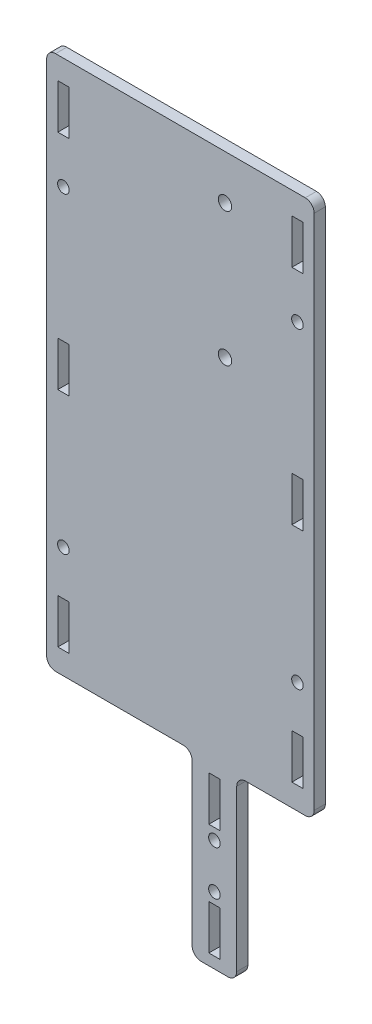
SolidWorks part; units mm, degrees
ref_plane "Front Plane" through (0, 0, 0) normal (0, 0, 1) x (1, 0, 0)
ref_plane "Top Plane" through (0, 0, 0) normal (0, 1, 0) x (1, 0, 0)
ref_plane "Right Plane" through (0, 0, 0) normal (1, 0, 0) x (0, 0, -1)
sketch "Sketch1" plane through (0, 0, 0) normal (0, 0, 1) x (1, 0, 0)
  line L0 (47.7875, -50.8) -> (47.7875, 0) construction
  line L1 (0, 0) -> (76.2, 0)
  line L2 (0, 0) -> (0, 152.4)
  line L3 (0, 152.4) -> (76.2, 152.4)
  line L4 (76.2, 0) -> (76.2, 152.4)
  line L5 (41.4375, 0) -> (54.1375, 0)
  line L6 (41.4375, 0) -> (41.4375, -50.8)
  line L7 (41.4375, -50.8) -> (54.1375, -50.8)
  line L8 (54.1375, 0) -> (54.1375, -50.8)
  line L9 (41.4375, -25.4) -> (54.1375, -25.4) construction
  line L10 (46.2, -34.925) -> (49.375, -34.925)
  line L11 (46.2, -34.925) -> (46.2, -47.625)
  line L12 (46.2, -47.625) -> (49.375, -47.625)
  line L13 (49.375, -34.925) -> (49.375, -47.625)
  line L14 (46.2, -34.925) -> (49.375, -47.625) construction
  line L15 (46.2, -47.625) -> (49.375, -34.925) construction
  line L16 (46.2, -3.175) -> (49.375, -15.875) construction
  line L17 (46.2, -15.875) -> (49.375, -3.175) construction
  line L18 (49.375, -15.875) -> (49.375, -3.175)
  line L19 (46.2, -3.175) -> (49.375, -3.175)
  line L20 (46.2, -15.875) -> (46.2, -3.175)
  line L21 (46.2, -15.875) -> (49.375, -15.875)
  point P11 (47.7875, -41.275)
  point P22 (47.7875, -9.525)
  dimension "D1" = 76.2
  dimension "D2" = 152.4
  dimension "D3" = 50.8
  dimension "D4" = 12.7
  dimension "D5" = 3.175
  dimension "D6" = 19.05
  dimension "D7" = 12.7
  dimension "D8" = 30
extrude "Boss-Extrude1" add sketch "Sketch1" along normal blind 3.175 contours L1 L4 L3 L2 | L8 L1 L6 L7 L21 L20 L19 L18 L10 L13 L12 L11 region at (38.1, 76.2, 0) region at (47.7875, -25.4, 0)
sketch "Sketch3" plane through (0, 0, 3.175) normal (0, 0, 1) x (1, 0, 0)
  line L0 (38.1, 152.4) -> (38.1, 0) construction
  line L1 (0, 76.2) -> (76.2, 76.2) construction
  line L2 (4.7625, 19.05) -> (4.7625, 133.35) construction
  line L3 (3.175, 146.05) -> (6.35, 146.05)
  line L4 (3.175, 146.05) -> (3.175, 133.35)
  line L5 (3.175, 133.35) -> (6.35, 133.35)
  line L6 (6.35, 146.05) -> (6.35, 133.35)
  line L7 (3.175, 19.05) -> (6.35, 19.05)
  line L8 (0, 0) -> (41.4375, 0)
  line L9 (41.4375, 0) -> (41.4375, -50.8)
  line L10 (41.4375, -50.8) -> (54.1375, -50.8)
  line L11 (54.1375, -50.8) -> (54.1375, 0)
  line L12 (54.1375, 0) -> (76.2, 0)
  line L13 (76.2, 0) -> (76.2, 152.4)
  line L14 (76.2, 152.4) -> (0, 152.4)
  line L15 (0, 152.4) -> (0, 0)
  line L16 (0, 0) -> (41.4375, 0)
  line L17 (41.4375, 0) -> (41.4375, -50.8)
  line L18 (41.4375, -50.8) -> (54.1375, -50.8)
  line L19 (54.1375, -50.8) -> (54.1375, 0)
  line L20 (54.1375, 0) -> (76.2, 0)
  line L21 (76.2, 0) -> (76.2, 152.4)
  line L22 (76.2, 152.4) -> (0, 152.4)
  line L23 (0, 152.4) -> (0, 0)
  line L24 (3.175, 19.05) -> (3.175, 6.35)
  line L25 (3.175, 6.35) -> (6.35, 6.35)
  line L26 (6.35, 19.05) -> (6.35, 6.35)
  line L27 (3.175, 82.55) -> (6.35, 82.55)
  line L28 (3.175, 82.55) -> (3.175, 69.85)
  line L29 (3.175, 69.85) -> (6.35, 69.85)
  line L30 (6.35, 82.55) -> (6.35, 69.85)
  line L31 (3.175, 82.55) -> (6.35, 69.85) construction
  line L32 (3.175, 69.85) -> (6.35, 82.55) construction
  line L33 (73.025, 69.85) -> (69.85, 82.55) construction
  line L34 (73.025, 82.55) -> (69.85, 69.85) construction
  line L35 (71.4375, 19.05) -> (71.4375, 133.35) construction
  line L36 (69.85, 82.55) -> (69.85, 69.85)
  line L37 (73.025, 69.85) -> (69.85, 69.85)
  line L38 (73.025, 82.55) -> (73.025, 69.85)
  line L39 (73.025, 82.55) -> (69.85, 82.55)
  line L40 (69.85, 19.05) -> (69.85, 6.35)
  line L41 (73.025, 6.35) -> (69.85, 6.35)
  line L42 (73.025, 19.05) -> (73.025, 6.35)
  line L43 (73.025, 19.05) -> (69.85, 19.05)
  line L44 (69.85, 146.05) -> (69.85, 133.35)
  line L45 (73.025, 133.35) -> (69.85, 133.35)
  line L46 (73.025, 146.05) -> (73.025, 133.35)
  line L47 (73.025, 146.05) -> (69.85, 146.05)
  circle A0 centre (4.7625, 120.65) radius 1.651
  circle A1 centre (4.7625, 31.75) radius 1.651
  circle A2 centre (71.4375, 31.75) radius 1.651
  circle A3 centre (71.4375, 120.65) radius 1.651
  point P20 (4.7625, 76.2)
  point P49 (71.4375, 76.2)
  dimension "D7" = 3.302
  dimension "D2" = 12.7
  dimension "D3" = 3.175
  dimension "D4" = 6.35
  dimension "D5" = 6.35
  dimension "D6" = 3.175
  dimension "D8" = 12.7
  dimension "D1" = 0
extrude "Cut-Extrude3" cut sketch "Sketch3" against normal blind 3.175 contours L6 L3 L4 L5 | L26 L7 L24 L25 | L46 L47 L44 L45 | A0 | L27 L30 L29 L28 | A1 | L40 L41 L42 L43 | A2 | A3 | L36 L37 L38 L39 region at (4.7625, 139.7, 3.175) region at (4.7625, 12.7, 3.175) region at (71.4375, 139.7, 3.175)
sketch "Sketch4" plane through (0, 0, 3.175) normal (0, 0, 1) x (1, 0, 0)
  line L0 (47.7875, -15.875) -> (47.7875, -34.925) construction
  line L1 (46.2, -15.875) -> (49.375, -15.875) construction
  line L2 (46.2, -34.925) -> (49.375, -34.925) construction
  line L3 (41.4375, -25.4) -> (54.1375, -25.4) construction
  line L4 (41.4375, 0) -> (41.4375, -50.8) construction
  line L5 (54.1375, 0) -> (54.1375, -50.8) construction
  circle A0 centre (47.7875, -19.05) radius 1.651
  circle A1 centre (47.7875, -31.75) radius 1.651
  dimension "D1" = 3.302
  dimension "D2" = 12.7
extrude "Cut-Extrude4" cut sketch "Sketch4" against normal blind 3.175
fillet "Fillet1" radius 2.54 8 edges at (76.2, 152.4, 1.5875) (76.2, 0, 1.5875) (54.1375, 0, 1.5875) (54.1375, -50.8, 1.5875) (41.4375, -50.8, 1.5875) (41.4375, 0, 1.5875) (0, 0, 1.5875) (0, 152.4, 1.5875)
sketch "Sketch5" plane through (0, 0, 3.175) normal (0, 0, 1) x (1, 0, 0)
  line L0 (50.8, 152.4) -> (50.8, 0) construction
  line L1 (2.54, 152.4) -> (73.66, 152.4) construction
  line L2 (56.6775, 0) -> (73.66, 0) construction
  line L3 (76.2, 2.54) -> (76.2, 149.86) construction
  circle A0 centre (50.8, 139.7) radius 1.905
  circle A1 centre (50.8, 101.6) radius 1.905
  dimension "D2" = 3.81
  dimension "D1" = 25.4
  dimension "D3" = 38.1
  dimension "D4" = 12.7
extrude "Cut-Extrude5" cut sketch "Sketch5" against normal blind 3.175
